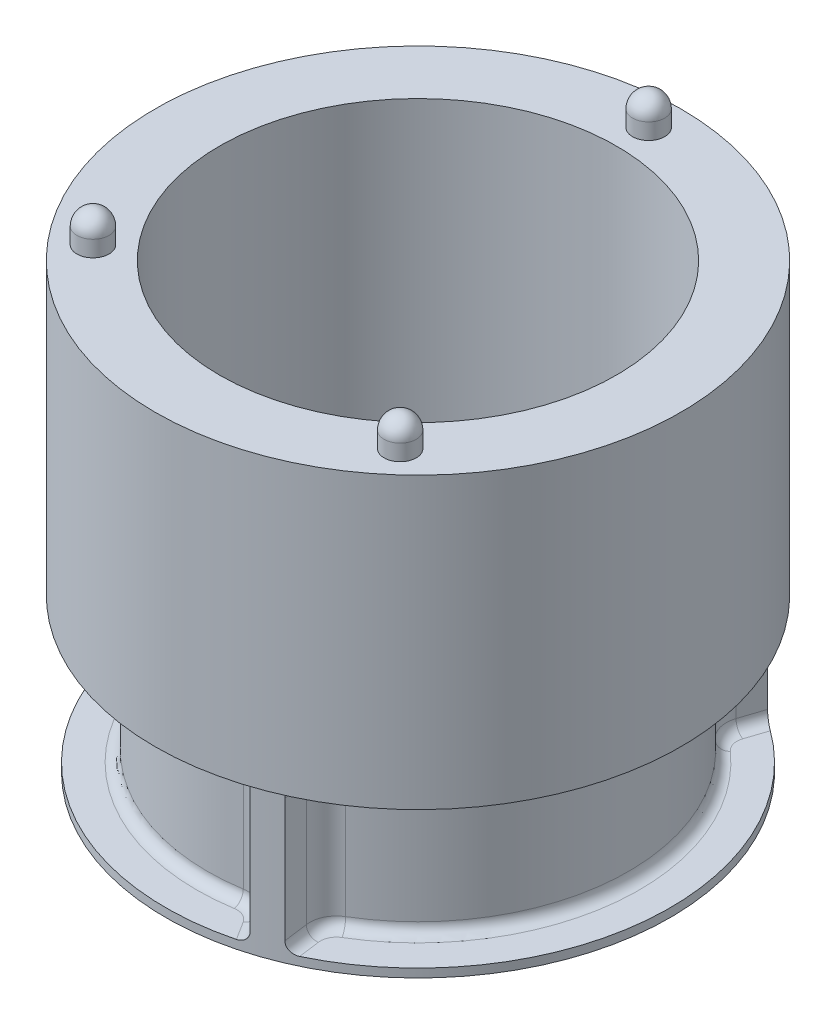
SolidWorks part; units mm, degrees
ref_plane "Front Plane" through (0, 0, 0) normal (0, 0, 1) x (1, 0, 0)
ref_plane "Top Plane" through (0, 0, 0) normal (0, 1, 0) x (1, 0, 0)
ref_plane "Right Plane" through (0, 0, 0) normal (1, 0, 0) x (0, 0, -1)
sketch "Sketch1" plane through (0, 0, 0) normal (0, 1, 0) x (1, 0, 0)
  line L0 (0, 41.6845) -> (0, -45.407) construction
  circle A0 centre (0, 0) radius 24.5
  circle A1 centre (0, 0) radius 18.5
  dimension "D1" = 49
  dimension "D2" = 6
extrude "Boss-Extrude1" add sketch "Sketch1" against normal blind 27
sketch "Sketch2" plane through (0, -27, 0) normal (0, -1, 0) x (1, 0, 0)
  circle A0 centre (0, 0) radius 18.125
  circle A1 centre (0, 0) radius 19.625
  dimension "D1" = 39.25
  dimension "D2" = 36.25
extrude "Boss-Extrude2" add sketch "Sketch2" along normal blind 13.5
sketch "Sketch3" plane through (0, 0, 0) normal (0, 1, 0) x (1, 0, 0)
  line L0 (0, 27.6464) -> (0, -26.5314) construction
  line L1 (0, 21.5) -> (-16.4266, -13.8718) construction
  line L2 (10.2687, 24.5) -> (-12.0375, 24.5) construction
  line L3 (-16.4266, -13.8718) -> (-21.3825, -18.0442) construction
  line L4 (-18.638, -15.9021) -> (-19.9023, -14.4202) construction
  circle A0 centre (0, 21.5) radius 1.5
  circle A1 centre (0, 0) radius 24.5 construction
  circle A2 centre (-16.4266, -13.8718) radius 1.5
  circle A3 centre (16.4263, -13.8718) radius 1.5 construction
  circle A4 centre (0, 0) radius 21.5 construction
  circle A5 centre (14.3499, -16.0103) radius 1.5
  dimension "D1" = 3
  dimension "D3" = 3
  dimension "D4" = 3
  dimension "D5" = 3
  dimension "D7" = 3
  dimension "D2" = 39
sketch "Sketch4" plane through (0, -40.5, 0) normal (0, -1, 0) x (1, 0, 0)
  circle A0 centre (0, 0) radius 23.5
  circle A1 centre (0, 0) radius 18.125
  circle A2 centre (0, 0) radius 18.125 construction
  dimension "D1" = 47
extrude "Boss-Extrude3" add sketch "Sketch4" along normal blind 0.8
extrude "Boss-Extrude4" add sketch "Sketch3" along normal blind 3
fillet "Fillet1" radius 1.5 3 edges at (-16.4266, 3, 15.3718) (0, 3, -20) (14.3499, 3, 17.5103)
sketch "Sketch6" plane through (0, -27, 0) normal (0, -1, 0) x (1, 0, 0)
  line L0 (0, 26.6626) -> (0, -27.0561) construction
  line L1 (6.8515, -14.8672) -> (11.7592, -23.3676) construction
  line L2 (0, 0) -> (12.7076, 34.9137) construction
  line L3 (8.6804, -12.0349) -> (14.7666, -22.5766) construction
  line L4 (0, 0) -> (20.132, -34.8697) construction
  line L5 (10.427, -21.0601) -> (6.8803, -17.173)
  line L6 (9.209, 21.6204) -> (8.5077, 16.4277)
  line L7 (6.8428, 22.4817) -> (4.0422, 18.053)
  line L8 (13.0251, -19.5601) -> (11.38, -14.5858)
  arc A0 (6.8803, -17.173) -> (11.38, -14.5858) centre (0, 0) ccw
  arc A1 (10.427, -21.0601) -> (13.0251, -19.5601) centre (0, 0) ccw
  circle A2 centre (0, 0) radius 23.5 construction
  circle A3 centre (0, 0) radius 18.5 construction
  arc A6 (8.5077, 16.4277) -> (4.0422, 18.053) centre (0, 0) ccw
  arc A11 (9.209, 21.6204) -> (6.8428, 22.4817) centre (0, 0) ccw
  dimension "D2" = 160
  dimension "D3" = 3
  dimension "D1" = 30
  dimension "D5" = 1.5
  dimension "D7" = 4.9743
extrude "Boss-Extrude14" add sketch "Sketch6" along normal up to surface (13.5 mm away) up to face at (0, -40.5, -23.5)
fillet "Fillet3" radius 2.5 4 edges at (4.6785, -33.75, 19.0592) (7.6868, -33.75, -18.0569) (11.7537, -33.75, -15.7159) (8.667, -33.75, 17.6075)
fillet "Fillet4" radius 1 20 edges at (12.6595, -40.5, -18.4547) (12.2537, -40.5, -15.9137) (9.0531, -40.5, 20.4661) (9.1218, -40.5, 17.8936) (6.2202, -40.5, 21.4972) (4.5141, -40.5, 19.5706) (9.6282, -40.5, -20.1846) (7.6133, -40.5, -18.5751) (19.5413, -40.5, 1.8104) (-19.5599, -40.5, -1.597) (6.2202, -27, 21.4972) (4.5141, -27, 19.5706) (9.6282, -27, -20.1846) (7.6133, -27, -18.5751) (12.6595, -27, -18.4547) (12.2537, -27, -15.9137) (9.0531, -27, 20.4661) (9.1218, -27, 17.8936) (-19.5599, -27, -1.597) (19.5413, -27, 1.8104)
